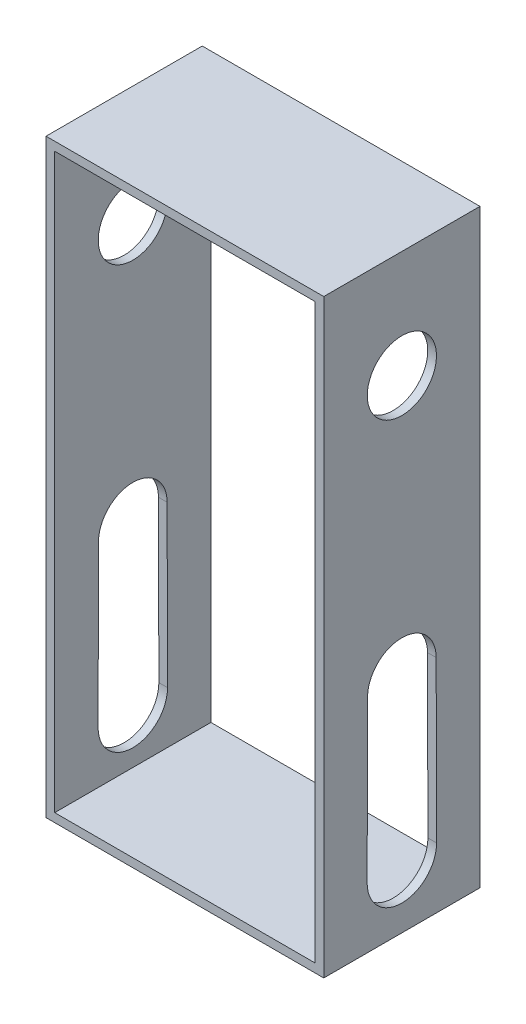
SolidWorks part; units mm, degrees
ref_plane "Front Plane" through (0, 0, 0) normal (0, 0, 1) x (1, 0, 0)
ref_plane "Top Plane" through (0, 0, 0) normal (0, 1, 0) x (1, 0, 0)
ref_plane "Right Plane" through (0, 0, 0) normal (1, 0, 0) x (0, 0, -1)
sketch "Sketch1" plane through (0, 0, 0) normal (0, 0, 1) x (1, 0, 0)
  line L1 (-101.6, -215.9) -> (101.6, -215.9)
  line L2 (-101.6, -215.9) -> (-101.6, 215.9)
  line L3 (-101.6, 215.9) -> (101.6, 215.9)
  line L4 (101.6, -215.9) -> (101.6, 215.9)
  line L5 (-101.6, -215.9) -> (101.6, 215.9) construction
  line L6 (-101.6, 215.9) -> (101.6, -215.9) construction
  line L7 (95.25, -209.55) -> (-95.25, -209.55)
  line L8 (95.25, -209.55) -> (95.25, 209.55)
  line L9 (95.25, 209.55) -> (-95.25, 209.55)
  line L10 (-95.25, -209.55) -> (-95.25, 209.55)
  line L11 (95.25, -209.55) -> (-95.25, 209.55) construction
  line L12 (95.25, 209.55) -> (-95.25, -209.55) construction
  point P0 (0, 0)
  point P8 (0, 0)
  dimension "D1" = 203.2
  dimension "D2" = 431.8
  dimension "D3" = 419.1
  dimension "D4" = 190.5
extrude "Boss-Extrude4" add sketch "Sketch1" along normal blind 114.3
sketch "Sketch4" plane through (0, 0, 0) normal (1, 0, 0) x (0, 0, -1)
  line L0 (0, 215.9) -> (-65.1381, -30.1772)
  line L1 (0, -215.9) -> (-31.9431, -95.2261)
  line L2 (-57.15, 0) -> (-57.15, 111.8999)
  line L3 (-114.3, 215.9) -> (0, 215.9) construction
  line L4 (-57.15, 0) -> (-114.3, 0)
  line L5 (-114.3, 215.9) -> (-114.3, -215.9) construction
  line L6 (-114.3, 0) -> (-80.5405, 127.5361)
  line L7 (-57.15, 215.9) -> (-41.6105, 157.1952)
  line L8 (0, 215.9) -> (-35.0877, 149.6233)
  line L9 (-114.3, 215.9) -> (-79.2123, 149.6233)
  line L10 (-57.15, 107.95) -> (-57.15, -28.8724)
  line L11 (-114.3, -215.9) -> (0, -215.9) construction
  line L12 (0, -215.9) -> (-31.7898, -155.8525)
  line L13 (0, 0) -> (-32.0309, -60.5027)
  line L14 (0, 0) -> (-57.15, 0)
  line L15 (-82.2526, -53.975) -> (-82.55, -171.6081)
  line L16 (-32.0474, -53.975) -> (-31.75, -171.6081)
  line L17 (-82.5102, -155.8525) -> (-114.3, -215.9)
  line L18 (-49.1619, -30.1772) -> (-114.3, 215.9)
  line L19 (-57.15, -197.0081) -> (-57.15, -215.9)
  line L20 (-82.2691, -60.5027) -> (-114.3, 0)
  line L21 (-82.3569, -95.2261) -> (-114.3, -215.9)
  line L22 (-57.15, 162.5264) -> (-57.15, 215.9)
  line L23 (-55.0109, 111.9905) -> (-114.3, 0)
  line L24 (-33.7595, 127.5361) -> (0, 0)
  line L25 (-72.6895, 157.1952) -> (-57.15, 215.9)
  line L26 (-59.2891, 111.9905) -> (0, 0)
  circle A0 centre (-57.15, 137.2131) radius 25.3132
  arc A1 (-32.0474, -53.975) -> (-82.2526, -53.975) centre (-57.15, -53.975) ccw
  arc A2 (-82.5497, -171.4797) -> (-31.7503, -171.4797) centre (-57.15, -171.6081) ccw
  point P34 (-57.15, 171.2052)
  point P42 (-57.15, 154.5708)
  point P43 (-57.15, 141.5526)
  point P44 (-57.15, 137.2131)
extrude "Cut-Extrude3" cut sketch "Sketch4" along normal blind 141.986 and the other way blind 204.216 contours A0 | L15 A2 L16 A1 L2 region at (0, -113.1003, 57.15) region at (0, 137.2131, 57.15)
